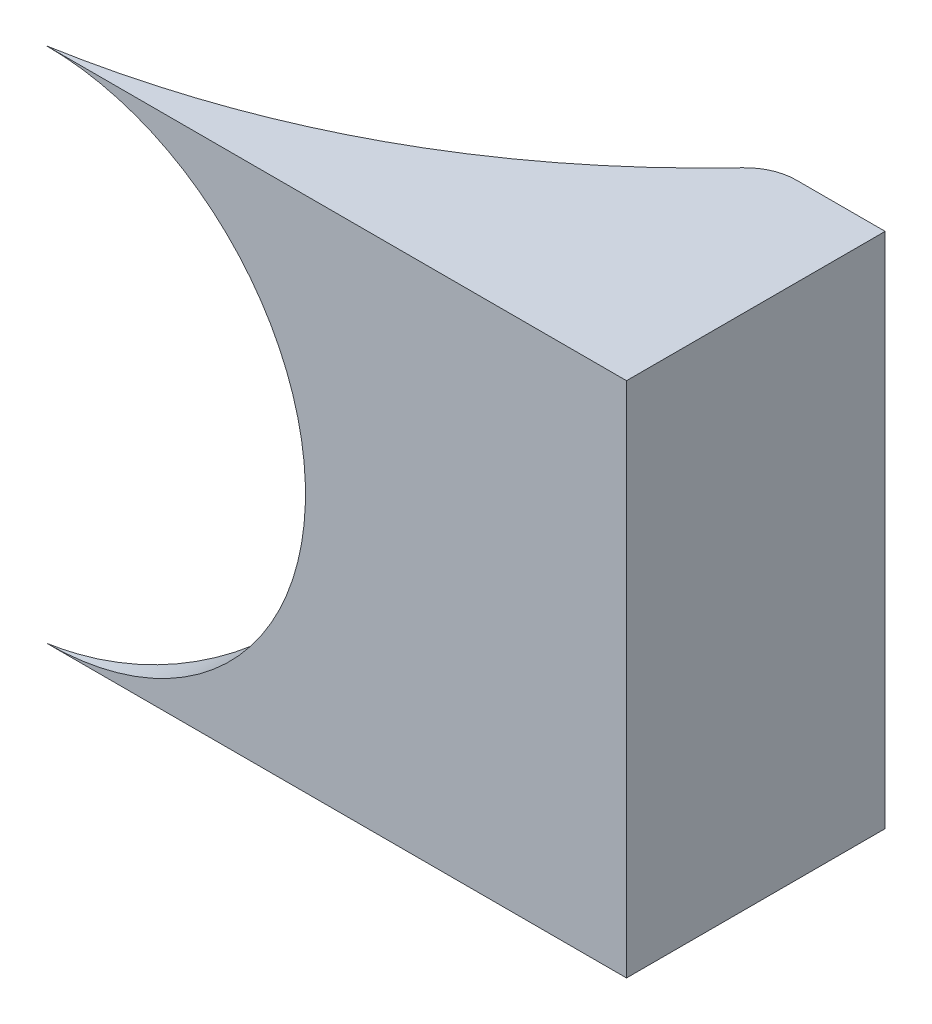
SolidWorks part; units mm, degrees
ref_plane "Front Plane" through (0, 0, 0) normal (0, 0, 1) x (1, 0, 0)
ref_plane "Top Plane" through (0, 0, 0) normal (0, 1, 0) x (1, 0, 0)
ref_plane "Right Plane" through (0, 0, 0) normal (1, 0, 0) x (0, 0, -1)
sketch "Sketch1" plane through (0, 0, 0) normal (0, 0, 1) x (1, 0, 0)
  line L0 (0, -1067.9916) -> (0, 52331.5874) construction
  line L1 (-1067.9916, 0) -> (52331.5874, 0) construction
  line L6 (0, 50) -> (112.0608, 50)
  line L7 (112.0608, 50) -> (112.0608, -50)
  line L8 (112.0608, -50) -> (0, -50)
  circle A1 centre (0, 0) radius 50
  dimension "D1" = 100
  dimension "D2" = 100
extrude "Boss-Extrude1" add sketch "Sketch1" along normal blind 50 contours A1 L8 L7 L6 region at (74.8099, 0, 0)
sketch "Sketch2" plane through (0, 0, 0) normal (0, 1, 0) x (1, 0, 0)
  line L3 (0, 0) -> (112.0608, 0) construction
  line L4 (90.4904, 0) -> (0, 0)
  line L5 (0, 0) -> (0, -50)
  spline S0 degree 2 poles (0, -50) (54.3212, -40.5055) (90.4904, 0) knots 0 0 0 1 1 1
extrude "Cut-Extrude1" cut sketch "Sketch2" against normal blind 98 and the other way blind 122
fillet "Fillet1" radius 10 1 edges at (90.4904, 0, 0)
